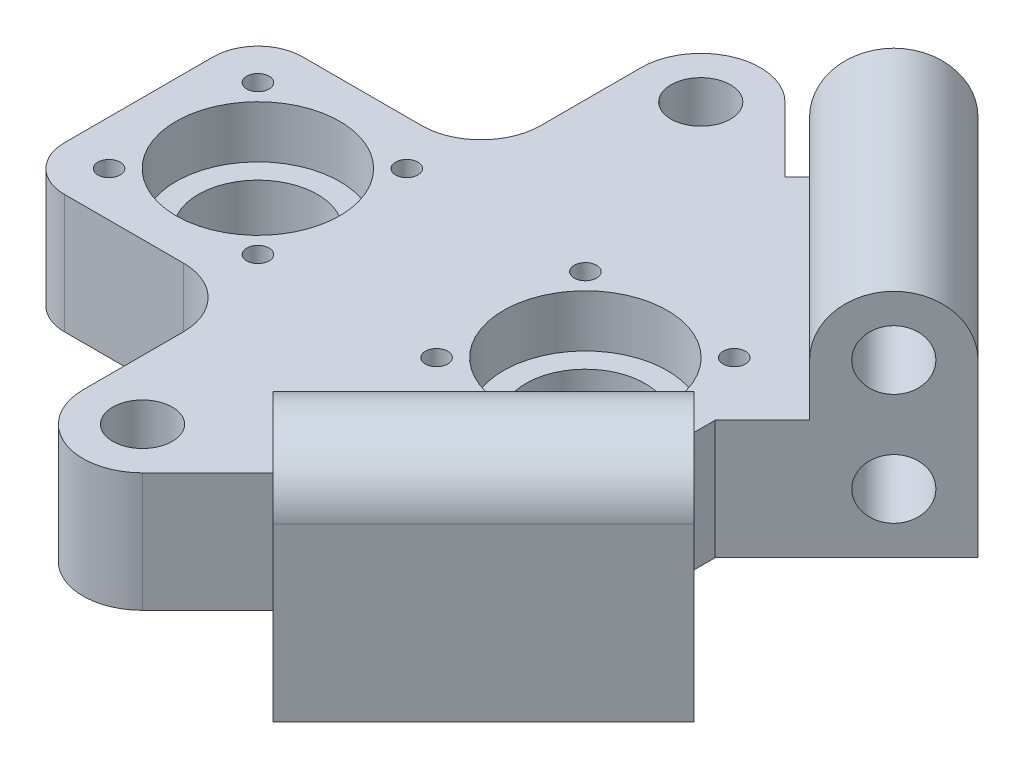
SolidWorks part; units mm, degrees
material "ABS"
ref_plane "Front Plane" through (0, 0, 0) normal (0, 0, 1) x (1, 0, 0)
ref_plane "Top Plane" through (0, 0, 0) normal (0, 1, 0) x (1, 0, 0)
ref_plane "Right Plane" through (0, 0, 0) normal (1, 0, 0) x (0, 0, -1)
sketch "Sketch1" plane through (0, 0, 0) normal (0, 1, 0) x (1, 0, 0)
  line L0 (-386.3027, 0) -> (412.614, 0) construction
  line L1 (0, -323.8826) -> (0, 265.8262) construction
  line L2 (0, 251.091) -> (251.091, 0)
  line L3 (160, 0) -> (80, 138.5641)
  line L4 (160, 0) -> (0, 0)
  line L5 (0, 239.7773) -> (239.7773, 0)
  line L6 (196.4046, 34.4091) -> (187.6569, 43.1569)
  line L7 (144, -10) -> (144, 10)
  line L8 (150, 16) -> (166, 16)
  line L9 (174, 24) -> (174, 37.5)
  line L11 (196.4046, 34.4091) -> (209.3717, 47.3762)
  line L12 (209.3717, 47.3762) -> (237.6559, 19.0919)
  line L13 (237.6559, 19.0919) -> (220, 1.4359)
  line L14 (220, 1.4359) -> (220, -1.4359)
  line L15 (237.6559, -19.0919) -> (220, -1.4359)
  line L16 (209.3717, -47.3762) -> (237.6559, -19.0919)
  line L17 (196.4046, -34.4091) -> (209.3717, -47.3762)
  line L18 (187.6569, -43.1569) -> (196.4046, -34.4091)
  line L19 (174, -24) -> (174, -37.5)
  line L20 (150, -16) -> (166, -16)
  circle A0 centre (0, 0) radius 160
  circle A1 centre (160, 0) radius 11
  circle A2 centre (150, 10) radius 1.5
  circle A3 centre (170, 10) radius 1.5
  circle A4 centre (170, -10) radius 1.5
  circle A5 centre (150, -10) radius 1.5
  circle A6 centre (204, 0) radius 11
  circle A7 centre (182, 37.5) radius 4
  circle A8 centre (80, 138.5641) radius 15
  circle A9 centre (194, 10) radius 1.5
  circle A10 centre (214, 10) radius 1.5
  circle A11 centre (214, -10) radius 1.5
  circle A12 centre (194, -10) radius 1.5
  arc A13 (144, 10) -> (150, 16) centre (150, 10) cw
  arc A14 (174, 37.5) -> (187.6569, 43.1569) centre (182, 37.5) cw
  arc A15 (166, 16) -> (174, 24) centre (166, 24) ccw
  circle A16 centre (182, -37.5) radius 4
  arc A17 (174, -37.5) -> (187.6569, -43.1569) centre (182, -37.5) ccw
  arc A18 (166, -16) -> (174, -24) centre (166, -24) cw
  arc A19 (144, -10) -> (150, -16) centre (150, -10) ccw
  circle A20 centre (160, 0) radius 8
  circle A21 centre (204, 0) radius 8
  point P53 (220, 0)
  point P65 (144, 0)
  dimension "D1" = 320
  dimension "D2" = 22
  dimension "D5" = 3
  dimension "D10" = 22
  dimension "D13" = 30
  dimension "D11" = 8
  dimension "D14" = 8
  dimension "D18" = 3
  dimension "D25" = 6
  dimension "D28" = 8
  dimension "D33" = 16
  dimension "D34" = 16
  dimension "D3" = 10
  dimension "D4" = 10
  dimension "D8" = 45
  dimension "D9" = 160
  dimension "D12" = 37.5
  dimension "D15" = 15
  dimension "D16" = 44
  dimension "D17" = 22
  dimension "D19" = 10
  dimension "D20" = 10
  dimension "D23" = 16
  dimension "D24" = 16
  dimension "D26" = 8
  dimension "D29" = 4
  dimension "D31" = 16
  dimension "D32" = 40
  dimension "D6" = 2
  dimension "D7" = 2
  dimension "D21" = 2
  dimension "D22" = 2
extrude "Boss-Extrude1" add sketch "Sketch1" along normal blind 16 contours L20 A18 L19 A17 L18 L17 L16 L15 L14 L13 L5 L11 A14 L9 A15 L8 A0 A1 A16 A12 A11 A10 A9 A7 A6 A4 A3 | A13 L7 L4 A1 L3 L8 A2 | A1 A0 L8 L3 | L7 A19 L20 A0 A1 L4 A5 | L13 L2 L11 L5 | L13 L12 L11 L2 region at (222.0996, 0, -31.8198) region at (217.857, 0, -27.5772) region at (214.1688, 0, -23.889) region at (154.599, 0, 15.7764) region at (155.7484, 0, -13.3869) region at (147.953, 0, -8.215)
extrude "Boss-Extrude2" add sketch "Sketch1<4>" along normal blind 9 contours A6 A21 region at (193.3111, 0, 0)
sketch "Sketch1<4>" plane through (0, 0, 0) normal (0, 1, 0) x (1, 0, 0) same geometry as "Sketch1"
sketch "Sketch2" plane through (109.282, 0, 109.282) normal (0.7071, 0, 0.7071) x (0.7071, 0, -0.7071)
  line L0 (181.5481, 16) -> (156.5789, 16) construction
  line L1 (181.5481, 16) -> (181.5481, 0) construction
  circle A0 centre (173.5481, 8) radius 4
  dimension "D1" = 8
  dimension "D2" = 8
  dimension "D3" = 8
extrude "Cut-Extrude1" cut sketch "Sketch2" against normal through all
sketch "Sketch3" plane through (109.282, 0, -109.282) normal (0.7071, 0, -0.7071) x (-0.7071, 0, -0.7071)
  line L0 (-181.5481, 16) -> (-181.5481, 0) construction
  line L1 (-181.5481, 0) -> (-156.5789, 0) construction
  circle A0 centre (-173.5481, 8) radius 4
  dimension "D1" = 8
  dimension "D2" = 8
  dimension "D3" = 8
extrude "Cut-Extrude2" cut sketch "Sketch3" against normal through all
ref_point "Point1"
extrude "Boss-Extrude3" add sketch "Sketch1<5>" along normal blind 9 contours A20 A0 A1 | A20 L4 A1 A0 | A20 L3 A1 L4 | A20 A0 A1 L3 region at (153.7862, 0, 6.029) region at (159.9652, 0, 9.5106) region at (157.4093, 0, -9.1164) region at (152.0783, 0, -4.5736)
sketch "Sketch1<5>" plane through (0, 0, 0) normal (0, 1, 0) x (1, 0, 0) same geometry as "Sketch1"
sketch "Sketch4" plane through (0, 0, 0) normal (0, -1, 0) x (1, 0, 0)
  line L1 (153.4641, 10) -> (151.7321, 13)
  line L2 (151.7321, 13) -> (148.2679, 13)
  line L3 (148.2679, 13) -> (146.5359, 10)
  line L4 (146.5359, 10) -> (148.2679, 7)
  line L5 (148.2679, 7) -> (151.7321, 7)
  line L6 (151.7321, 7) -> (153.4641, 10)
  line L7 (173.4641, 10) -> (171.7321, 13)
  line L8 (171.7321, 13) -> (168.2679, 13)
  line L9 (168.2679, 13) -> (166.5359, 10)
  line L10 (166.5359, 10) -> (168.2679, 7)
  line L11 (168.2679, 7) -> (171.7321, 7)
  line L12 (171.7321, 7) -> (173.4641, 10)
  line L13 (153.4641, -10) -> (151.7321, -7)
  line L14 (151.7321, -7) -> (148.2679, -7)
  line L15 (148.2679, -7) -> (146.5359, -10)
  line L16 (146.5359, -10) -> (148.2679, -13)
  line L17 (148.2679, -13) -> (151.7321, -13)
  line L18 (151.7321, -13) -> (153.4641, -10)
  line L19 (173.4641, -10) -> (171.7321, -7)
  line L20 (171.7321, -7) -> (168.2679, -7)
  line L21 (168.2679, -7) -> (166.5359, -10)
  line L22 (166.5359, -10) -> (168.2679, -13)
  line L23 (168.2679, -13) -> (171.7321, -13)
  line L24 (171.7321, -13) -> (173.4641, -10)
  line L25 (197.4641, 10) -> (195.7321, 13)
  line L26 (195.7321, 13) -> (192.2679, 13)
  line L27 (192.2679, 13) -> (190.5359, 10)
  line L28 (190.5359, 10) -> (192.2679, 7)
  line L29 (192.2679, 7) -> (195.7321, 7)
  line L30 (195.7321, 7) -> (197.4641, 10)
  line L31 (217.4641, 10) -> (215.7321, 13)
  line L32 (215.7321, 13) -> (212.2679, 13)
  line L33 (212.2679, 13) -> (210.5359, 10)
  line L34 (210.5359, 10) -> (212.2679, 7)
  line L35 (212.2679, 7) -> (215.7321, 7)
  line L36 (215.7321, 7) -> (217.4641, 10)
  line L37 (197.4641, -10) -> (195.7321, -7)
  line L38 (195.7321, -7) -> (192.2679, -7)
  line L39 (192.2679, -7) -> (190.5359, -10)
  line L40 (190.5359, -10) -> (192.2679, -13)
  line L41 (192.2679, -13) -> (195.7321, -13)
  line L42 (195.7321, -13) -> (197.4641, -10)
  line L43 (217.4641, -10) -> (215.7321, -7)
  line L44 (215.7321, -7) -> (212.2679, -7)
  line L45 (212.2679, -7) -> (210.5359, -10)
  line L46 (210.5359, -10) -> (212.2679, -13)
  line L47 (212.2679, -13) -> (215.7321, -13)
  line L48 (215.7321, -13) -> (217.4641, -10)
  circle A0 centre (150, 10) radius 3 construction
  circle A1 centre (170, 10) radius 3 construction
  circle A2 centre (150, -10) radius 3 construction
  circle A3 centre (170, -10) radius 3 construction
  circle A4 centre (194, 10) radius 3 construction
  circle A5 centre (214, 10) radius 3 construction
  circle A6 centre (194, -10) radius 3 construction
  circle A7 centre (214, -10) radius 3 construction
extrude "Cut-Extrude3" cut sketch "Sketch4" against normal blind 2.5
sketch "Sketch5" plane through (80.9978, 0, -80.9978) normal (-0.7071, 0, 0.7071) x (0.7071, 0, 0.7071)
  line L0 (181.5481, 16) -> (181.5481, 23)
  line L1 (165.5481, 23) -> (165.5481, 16)
  line L2 (163.2099, 16) -> (181.5481, 16) construction
  line L3 (165.5481, 16) -> (181.5481, 16)
  circle A0 centre (173.5481, 23) radius 4
  circle A1 centre (173.5481, 8) radius 4 construction
  arc A2 (181.5481, 23) -> (165.5481, 23) centre (173.5481, 23) ccw
  dimension "D1" = 8
  dimension "D3" = 8
  dimension "D2" = 15
sketch "Sketch6" plane through (80.9978, 0, 80.9978) normal (-0.7071, 0, -0.7071) x (-0.7071, 0, 0.7071)
  line L0 (-165.5481, 16) -> (-165.5481, 23)
  line L1 (-181.5481, 23) -> (-181.5481, 16)
  line L2 (-181.5481, 16) -> (-165.5481, 16)
  circle A0 centre (-173.5481, 23) radius 4
  arc A1 (-165.5481, 23) -> (-181.5481, 23) centre (-173.5481, 23) ccw
  circle A2 centre (-173.5481, 8) radius 4 construction
  dimension "D1" = 8
  dimension "D2" = 8
  dimension "D3" = 15
extrude "Boss-Extrude4" add sketch "Sketch5" against normal up to surface (40 mm away) up to face at (229.1707, 8, 10.6066)
extrude "Boss-Extrude5" add sketch "Sketch6" against normal up to surface (40 mm away) up to face at (234.8275, 8, -16.2635)
equation "\"rod_diameter\"= 8"
equation "\"rod_hole_thickness\"= 4"
equation "\"rod_radius\"= \"rod_diameter\" / 2"
equation "\"platter_diameter\"= 320"
equation "\"platter_radius\"= \"platter_diameter\" / 2"
equation "\"extruder_mount_hole_spacing\"= 75"
equation "\"arm_rod_spacing\"= 40"
equation "\"D1@Sketch1\"=\"platter_diameter\""
equation "\"D9@Sketch1\"=\"platter_radius\""
equation "\"D11@Sketch1\"=\"rod_diameter\""
equation "\"D14@Sketch1\"=\"rod_diameter\""
equation "\"D12@Sketch1\"=\"z_rod_spacing\"/2"
equation "\"D26@Sketch1\"=\"rod_radius\"+\"rod_hole_thickness\""
equation "\"D28@Sketch1\"=\"rod_radius\"+\"rod_hole_thickness\""
equation "\"D29@Sketch1\"=\"rod_hole_thickness\""
equation "\"D1@Boss-Extrude2\"= \"D1@Boss-Extrude1\" - 7"
equation "\"D1@Sketch2\" = \"rod_diameter\""
equation "\"D2@Sketch2\"= \"D1@Boss-Extrude1\" / 2"
equation "\"D3@Sketch2\"=\"rod_radius\"+\"rod_hole_thickness\""
equation "\"D1@Sketch3\"=\"rod_diameter\""
equation "\"D2@Sketch3\"=\"rod_radius\"+\"rod_hole_thickness\""
equation "\"D3@Sketch3\"= \"D1@Boss-Extrude1\" / 2"
equation "\"D1@Boss-Extrude1\" = \"rod_diameter\" + \"rod_hole_thickness\" * 2"
equation "\"D1@Boss-Extrude3\"= \"D1@Boss-Extrude1\" - 7"
equation "\"D1@Sketch5\"=\"rod_diameter\""
equation "\"top_frame_rod_spacing\"= \"arm_rod_spacing\" + 40"
equation "\"motor_level_rod_spacing\"= 15"
equation "\"D2@Sketch5\"=\"motor_level_rod_spacing\""
equation "\"D3@Sketch5\"=\"rod_radius\"+\"rod_hole_thickness\""
equation "\"D3@Sketch6\"=\"motor_level_rod_spacing\""
equation "\"D1@Sketch6\"=\"rod_diameter\""
equation "\"D2@Sketch6\"=\"rod_radius\"+\"rod_hole_thickness\""
equation "\"linear_bearing_diameter\"= 15"
equation "\"platter_rod_spacing\"= 50"
equation "\"z_rod_spacing\"= 75"
